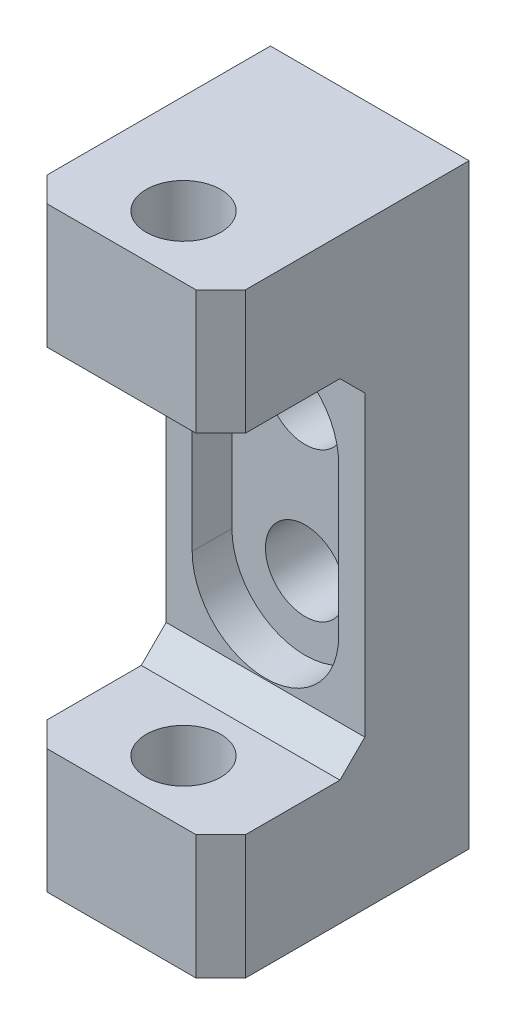
SolidWorks part; units mm, degrees
ref_plane "前视基准面" through (0, 0, 0) normal (0, 0, 1) x (1, 0, 0)
ref_plane "上视基准面" through (0, 0, 0) normal (0, 1, 0) x (1, 0, 0)
ref_plane "右视基准面" through (0, 0, 0) normal (1, 0, 0) x (0, 0, -1)
sketch "草图2" plane through (0, 0, 0) normal (0, 0, 1) x (1, 0, 0)
  line L0 (75, 105) -> (120, 105) construction
  line L1 (104, 105) -> (96, 105)
  line L2 (104, 105) -> (104, 81)
  line L3 (104, 81) -> (96, 81)
  line L4 (96, 105) -> (96, 81)
  line L6 (100, 81) -> (100, 105) construction
  line L7 (130, 95) -> (130, -95) construction
  dimension "D1" = 24
  dimension "D2" = 8
  dimension "D3" = 30
extrude "凸台-拉伸1" add sketch "草图2" along normal blind 10
sketch "草图3" plane through (96, 0, 0) normal (-1, 0, 0) x (0, 0, 1)
  line L0 (0, 93) -> (22.6575, 93) construction
  line L5 (0, 105) -> (0, 81) construction
  line L6 (10, 81) -> (0, 81) construction
  line L7 (4.2, 100) -> (13.3805, 100)
  line L8 (4.2, 100) -> (4.2, 86)
  line L9 (4.2, 86) -> (13.3805, 86)
  line L10 (13.3805, 100) -> (13.3805, 86)
  line L11 (4.2, 100) -> (13.3805, 86) construction
  line L12 (4.2, 86) -> (13.3805, 100) construction
  point P0 (8.7902, 93)
  dimension "D1" = 4.2
  dimension "D2" = 5
extrude "切除-拉伸1" cut sketch "草图3" against normal blind 40
sketch "草图4" plane through (0, 0, 4.2) normal (0, 0, 1) x (1, 0, 0)
  line L0 (100, 100) -> (100, 86) construction
  line L1 (104, 100) -> (96, 100) construction
  line L2 (104, 86) -> (96, 86) construction
  line L3 (100, 93) -> (104, 93) construction
  line L4 (104, 100) -> (104, 86) construction
  circle A0 centre (100, 96) radius 2
  circle A1 centre (100, 90) radius 2
  dimension "D1" = 4
  dimension "D2" = 6
chamfer "倒角1" distance 1 angle 45 2 edges at (100, 86, 4.2) (100, 100, 4.2)
sketch "草图6" plane through (0, 105, 0) normal (0, 1, 0) x (1, 0, 0)
  line L0 (100, -5.2) -> (100, -10) construction
  line L4 (104, -10) -> (104, -5.2)
  line L5 (104, -5.2) -> (96, -5.2)
  line L6 (96, -5.2) -> (96, -10)
  line L7 (96, -10) -> (104, -10)
  line L8 (104, -10) -> (104, -5.2) construction
  line L9 (104, -5.2) -> (96, -5.2) construction
  line L10 (96, -5.2) -> (96, -10) construction
  line L11 (96, -10) -> (104, -10) construction
  circle A1 centre (100, -7.5) radius 1.5
  point P6 (100, -7.0007)
  point P12 (97.9967, -6.6771)
  point P14 (100.9437, -6.75)
  point P15 (98.9526, -7.0947)
  point P16 (95.9935, -6.747)
  point P17 (101.1139, -7.0675)
  point P19 (96.4983, -6.6089)
  dimension "D2" = 3
  dimension "D3" = 2.5
  dimension "D1" = 0
hole_wizard "M3 六角头螺栓的柱形沉头孔1" positions "草图7" profile "草图8" counterbore size "M3" standard "GB" end condition through all
sketch "草图7" plane through (124.3639, -131.0101, 4.2) normal (0, 0, 1) x (0, 1, 0)
  point P0 (221.0101, 24.3639)
  point P3 (227.0101, 24.3639)
sketch "草图8" plane through (100, 90, 4.2) normal (1, 0, 0) x (0, -1, 0)
  line L0 (0, 0) -> (0, 4.2)
  line L1 (0, 4.2) -> (1.6, 4.2)
  line L2 (1.6, 4.2) -> (1.6, 1.6)
  line L3 (1.6, 1.6) -> (2.95, 1.6)
  line L4 (2.95, 1.6) -> (2.95, 0)
  line L5 (2.95, 0) -> (0, 0)
  line L6 (0, -6.35) -> (0, 107.95) construction
  dimension "通孔孔直径" = 3.2
  dimension "通孔孔深度" = 4.2
  dimension "柱形沉头孔直径" = 5.9
  dimension "柱形沉头孔深度" = 1.6
sketch "草图11" plane through (0, 0, 4.2) normal (0, 0, 1) x (1, 0, 0)
  line L0 (100, 90) -> (100, 96) construction
  line L1 (97.05, 90) -> (97.05, 96)
  line L2 (102.95, 90) -> (102.95, 96)
  arc A0 (97.05, 90) -> (102.95, 90) centre (100, 90) ccw
  arc A1 (102.95, 96) -> (97.05, 96) centre (100, 96) ccw
  point P2 (100, 93)
  dimension "D1" = 5.9
extrude "切除-拉伸2" cut sketch "草图11" against normal up to surface (1.6 mm away) up to face at (101.6, 90, 2.6)
hole_wizard "大小mm 暗销孔2" positions "草图12" profile "草图13" hole size "Ø3.0" standard "GB"
sketch "草图12" plane through (124.3639, 105, -5) normal (0, 1, 0) x (-1, 0, 0)
  point P0 (24.3639, 12.5)
sketch "草图13" plane through (100, 105, 7.5) normal (1, 0, 0) x (0, 0, 1)
  line L0 (0, 0) -> (0, 24.9013)
  line L1 (0, 24.9013) -> (1.5, 24)
  line L2 (1.5, 24) -> (1.5, 0)
  line L3 (1.5, 0) -> (0, 0)
  line L4 (0, 24.9013) -> (-1.5, 24) construction
  line L5 (0, -6.35) -> (0, 107.95) construction
  dimension "孔直径" = 3
  dimension "孔深度" = 24
  dimension "导头角度" = 118
chamfer "倒角2" distance 1 angle 45 4 edges at (96, 83.5, 10) (104, 83.5, 10) (104, 102.5, 10) (96, 102.5, 10)
